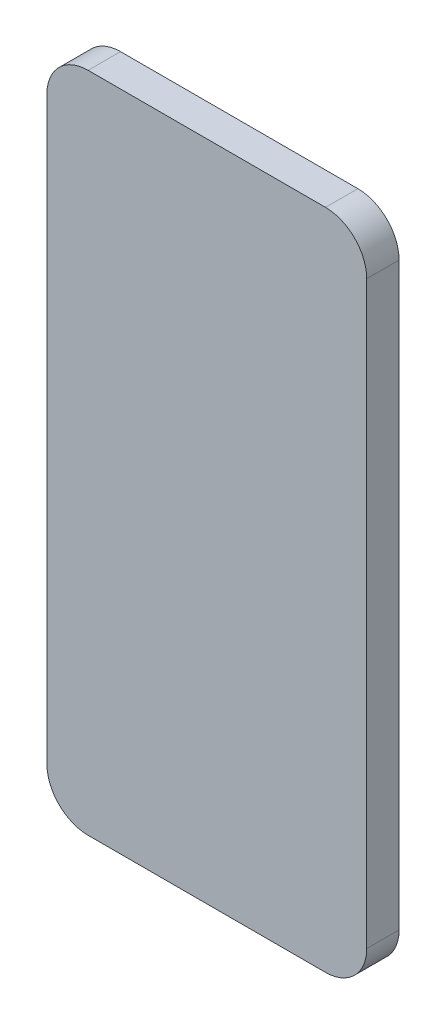
SolidWorks part; units mm, degrees
ref_plane "Ön Düzlem" through (0, 0, 0) normal (0, 0, 1) x (1, 0, 0)
ref_plane "Üst Düzlem" through (0, 0, 0) normal (0, 1, 0) x (1, 0, 0)
ref_plane "Sağ Düzlem" through (0, 0, 0) normal (1, 0, 0) x (0, 0, -1)
sketch "Çizim1" plane through (0, 0, 0) normal (0, 0, 1) x (1, 0, 0)
  line L1 (-22.8455, 30.2356) -> (54.7345, 30.2356)
  line L2 (-22.8455, 30.2356) -> (-22.8455, -130.4644)
  line L3 (-22.8455, -130.4644) -> (54.7345, -130.4644)
  line L4 (54.7345, 30.2356) -> (54.7345, -130.4644)
  dimension "D1" = 77.58
  dimension "D2" = 160.7
extrude "Yükseklik-Ekstrüzyon1" add sketch "Çizim1" along normal blind 7.85
fillet "Radyus1" radius 10 4 edges at (54.7345, -130.4644, 3.925) (-22.8455, -130.4644, 3.925) (-22.8455, 30.2356, 3.925) (54.7345, 30.2356, 3.925)
sketch "Çizim3" plane through (0, 0, 0) normal (0, 0, -1) x (-1, 0, 0)
  line L0 (-42.7345, 28.2356) -> (-22.7345, 28.2356)
  line L1 (-52.7345, 18.2356) -> (-52.7345, -1.7644)
  line L2 (-42.7345, -11.7644) -> (-22.7345, -11.7644)
  line L3 (-12.7345, 18.2356) -> (-12.7345, -1.7644)
  arc A0 (-42.7345, 28.2356) -> (-52.7345, 18.2356) centre (-42.7345, 18.2356) ccw
  arc A1 (-12.7345, 18.2356) -> (-22.7345, 28.2356) centre (-22.7345, 18.2356) ccw
  arc A2 (-22.7345, -11.7644) -> (-12.7345, -1.7644) centre (-22.7345, -1.7644) ccw
  arc A3 (-52.7345, -1.7644) -> (-42.7345, -11.7644) centre (-42.7345, -1.7644) ccw
  dimension "D1" = 2
  dimension "D2" = 2
extrude "Yükseklik-Ekstrüzyon2" add sketch "Çizim3" along normal blind 2
